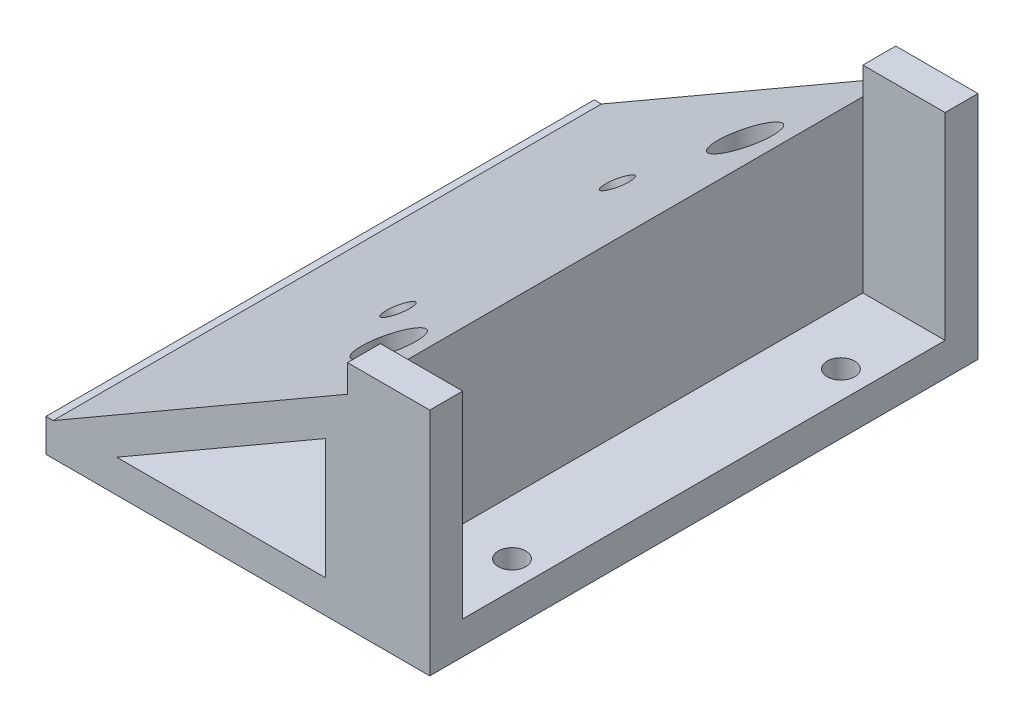
SolidWorks part; units mm, degrees
ref_plane "Front Plane" through (0, 0, 0) normal (0, 0, 1) x (1, 0, 0)
ref_plane "Top Plane" through (0, 0, 0) normal (0, 1, 0) x (1, 0, 0)
ref_plane "Right Plane" through (0, 0, 0) normal (1, 0, 0) x (0, 0, -1)
sketch "Sketch1" plane through (0, 0, 0) normal (0, 1, 0) x (1, 0, 0)
  line L1 (-70.1234, 23.0109) -> (-105.1234, 23.0109)
  line L2 (-70.1234, 23.0109) -> (-70.1234, 73.0109)
  line L3 (-70.1234, 73.0109) -> (-105.1234, 73.0109)
  line L4 (-105.1234, 23.0109) -> (-105.1234, 73.0109)
  dimension "D1" = 50
  dimension "D2" = 35
extrude "Boss-Extrude1" add sketch "Sketch1" along normal blind 3
sketch "Sketch2" plane through (0, 3, 0) normal (0, 1, 0) x (1, 0, 0)
  line L0 (-70.1234, 73.0109) -> (-105.1234, 73.0109) construction
  line L1 (-70.1234, 23.0109) -> (-70.1234, 73.0109) construction
  line L2 (-105.1234, 23.0109) -> (-70.1234, 23.0109) construction
  circle A1 centre (-82.6234, 64.264) radius 1.5
  circle A2 centre (-82.6234, 31.764) radius 1.5
  circle A3 centre (-72.6234, 33.0109) radius 1.25
  circle A4 centre (-72.6234, 63.0109) radius 1.25
  dimension "D8" = 3
  dimension "D9" = 3
  dimension "D10" = 2.5
  dimension "D11" = 2.5
  dimension "D1" = 30
  dimension "D2" = 32.5
  dimension "D3" = 10
  dimension "D4" = 10
  dimension "D5" = 10
  dimension "D6" = 2.5
  dimension "D7" = 2.5
  dimension "D12" = 8.7531
extrude "Cut-Extrude1" cut sketch "Sketch2" against normal through all
sketch "Sketch4" plane through (0, 0, -23.0109) normal (0, 0, 1) x (1, 0, 0)
  line L0 (-77.6234, 3) -> (-104.4702, 3)
  line L2 (-104.4702, 3) -> (-77.6234, 18.5)
  line L3 (-77.6234, 18.5) -> (-77.6234, 3)
  line L7 (-105.1234, 3) -> (-70.1234, 3) construction
  line L8 (-70.1234, 3) -> (-70.1234, 0) construction
  dimension "D1" = 31
  dimension "D2" = 30
  dimension "D3" = 60
  dimension "D4" = 7.5
extrude "Boss-Extrude2" add sketch "Sketch4" against normal blind 50 contours L0 L2 L3
sketch "Sketch6" plane through (0, 0, -23.0109) normal (0, 0, 1) x (1, 0, 0)
  line L0 (-98.676, 3) -> (-79.6234, 3)
  line L2 (-98.676, 3) -> (-79.6234, 14)
  line L3 (-79.6234, 14) -> (-79.6234, 3)
  line L10 (-77.6234, 3) -> (-70.1234, 3) construction
  dimension "D1" = 30
  dimension "D2" = 60
  dimension "D3" = 2
  dimension "D4" = 22
extrude "Cut-Extrude5" cut sketch "Sketch6" against normal through all contours L0 L3 L2
sketch "Sketch8" plane through (0, 3, 0) normal (0, 1, 0) x (1, 0, 0)
  circle A0 centre (-82.6234, 31.764) radius 2.5
  circle A1 centre (-82.6234, 31.764) radius 1.5 construction
  circle A2 centre (-82.6234, 64.264) radius 2.5
  circle A3 centre (-82.6234, 64.264) radius 1.5 construction
  dimension "D1" = 5
  dimension "D2" = 5
extrude "Cut-Extrude6" cut sketch "Sketch8" against normal blind 1 and the other way through all
sketch "Sketch9" plane through (-27.4166, 47.4869, 0) normal (-0.5, 0.866, 0) x (0.866, 0.5, 0)
  line L0 (-88.9739, 73.0109) -> (-57.9739, 73.0109) construction
  line L1 (-57.9739, 73.0109) -> (-57.9739, 23.0109) construction
  circle A0 centre (-69.9739, 58.0109) radius 1.25
  circle A1 centre (-69.9739, 38.0109) radius 1.25
  dimension "D1" = 2.5
  dimension "D2" = 2.5
  dimension "D3" = 20
  dimension "D4" = 15
  dimension "D5" = 12
  dimension "D6" = 12
extrude "Cut-Extrude7" cut sketch "Sketch9" against normal up to next
sketch "Sketch10" plane through (-25.968, 44.978, 0) normal (0.5, -0.866, 0) x (-0.866, -0.5, 0)
  circle A0 centre (69.9739, 58.0109) radius 2.5
  circle A1 centre (69.9739, 38.0109) radius 2.5
  circle A3 centre (69.9739, 38.0109) radius 1.25 construction
  circle A4 centre (69.9739, 58.0109) radius 1.25 construction
  dimension "D1" = 5
  dimension "D2" = 5
extrude "Cut-Extrude8" cut sketch "Sketch10" against normal blind 0.5 and the other way up to next
sketch "Sketch11" plane through (0, 3, 0) normal (0, 1, 0) x (1, 0, 0)
  line L0 (-77.6234, 23.0109) -> (-70.1234, 23.0109) construction
  line L1 (-70.1234, 23.0109) -> (-77.6234, 23.0109)
  line L2 (-70.1234, 23.0109) -> (-70.1234, 26.0109)
  line L3 (-70.1234, 26.0109) -> (-77.6234, 26.0109)
  line L4 (-77.6234, 23.0109) -> (-77.6234, 26.0109)
  line L5 (-70.1234, 70.0109) -> (-77.6234, 70.0109)
  line L6 (-70.1234, 70.0109) -> (-70.1234, 73.0109)
  line L7 (-70.1234, 73.0109) -> (-77.6234, 73.0109)
  line L8 (-77.6234, 70.0109) -> (-77.6234, 73.0109)
  line L9 (-70.1234, 73.0109) -> (-77.6234, 73.0109) construction
  line L10 (-70.1234, 23.0109) -> (-70.1234, 73.0109) construction
  line L11 (-77.6234, 73.0109) -> (-77.6234, 23.0109) construction
  dimension "D1" = 3
  dimension "D2" = 3
  dimension "D3" = 0
  dimension "D4" = 0
  dimension "D5" = 0
  dimension "D6" = 0
  dimension "D7" = 0
  dimension "D8" = 0
extrude "Boss-Extrude3" add sketch "Sketch11" along normal blind 18
